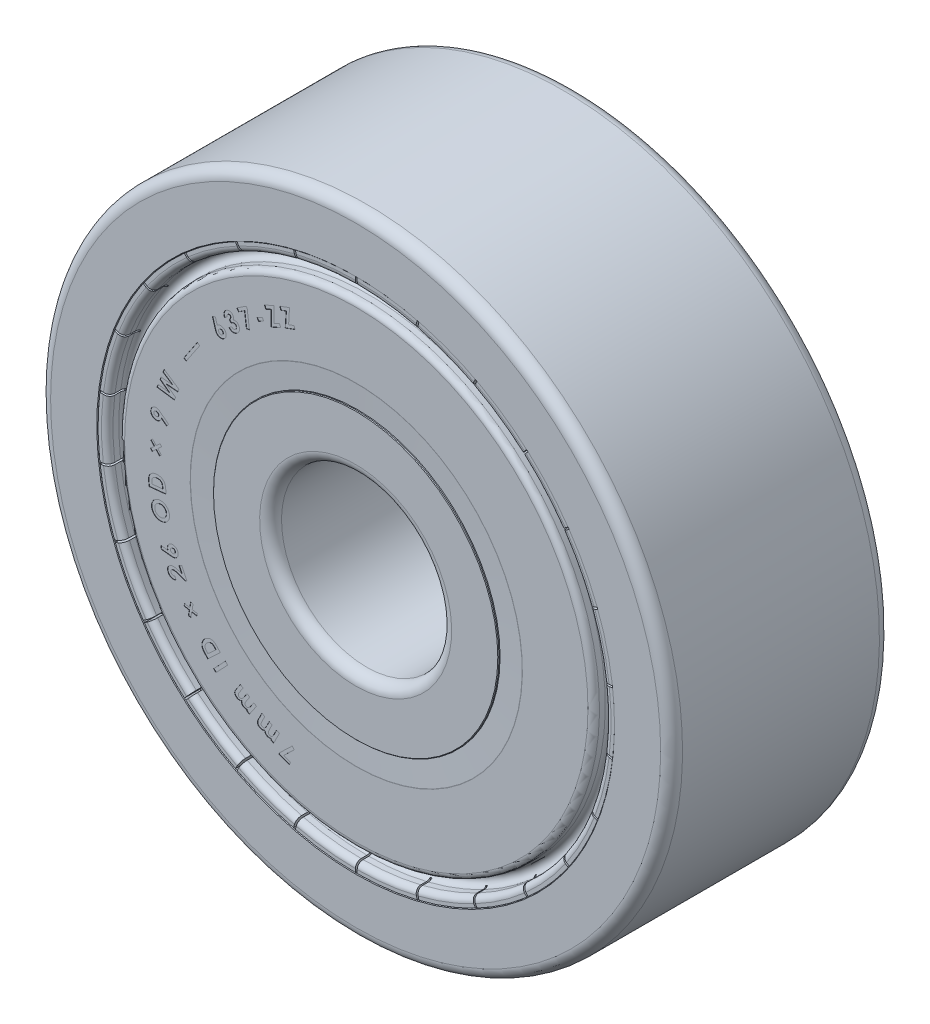
SolidWorks part; units mm, degrees
material "AISI 316 Annealed Stainless Steel Bar (SS)"
ref_plane "Front" through (0, 0, 0) normal (0, 0, 1) x (1, 0, 0)
ref_plane "Top" through (0, 0, 0) normal (0, 1, 0) x (1, 0, 0)
ref_plane "Right" through (0, 0, 0) normal (1, 0, 0) x (0, 0, -1)
sketch "LAYOUT R" plane through (0, 0, 0) normal (1, 0, 0) x (0, 0, -1)
  line L0 (-4.05, 3.5) -> (4.05, 3.5)
  line L1 (4.5, -13) -> (-4.5, -13) construction
  line L2 (4.5, -13) -> (4.5, 2.5781) construction
  line L3 (4.05, 13) -> (-4.05, 13)
  line L4 (-4.5, -13) -> (-4.5, 12.55) construction
  line L6 (2.6982, 0) -> (-2.6982, 0) construction
  line L7 (-4.474, 5.875) -> (4.474, 5.875)
  line L8 (-4.474, 10.625) -> (4.474, 10.625)
  line L11 (-8.89, 0) -> (8.89, 0) construction
  line L12 (-4.5, 12.55) -> (-4.5, 10.651)
  line L13 (4.5, 12.55) -> (4.5, 10.651)
  line L16 (-4.5, 5.849) -> (-4.5, 3.95)
  line L17 (4.5, 5.849) -> (4.5, 3.95)
  line L30 (-4.474, 10.625) -> (-4.474, 5.875) construction
  line L31 (4.474, 10.625) -> (4.474, 5.875) construction
  line L32 (-4.474, 6.825) -> (4.474, 6.825) construction
  line L33 (-4.4738, 6.825) -> (-4.4323, 5.875)
  line L34 (4.4738, 6.825) -> (4.4323, 5.875)
  line L35 (-4.474, 10.245) -> (4.474, 10.245) construction
  line L38 (-4.5, 10.651) -> (4.5, 10.651) construction
  line L39 (-4.474, 10.625) -> (-4.474, 10.4825)
  line L40 (-4.2365, 10.245) -> (-3.999, 10.245)
  line L41 (-4.474, 6.8354) -> (-4.474, 9.5325)
  line L42 (-4.2365, 9.77) -> (-3.999, 9.77)
  line L43 (4.474, 6.8354) -> (4.474, 9.5325)
  line L44 (4.2365, 9.77) -> (3.999, 9.77)
  line L45 (4.2365, 10.245) -> (3.999, 10.245)
  line L46 (-4.474, 9.77) -> (4.474, 9.77) construction
  line L50 (-1.3199, 9.675) -> (1.3199, 9.675) construction
  line L53 (4.474, 5.875) -> (4.5, 5.849)
  line L54 (-4.474, 5.875) -> (-4.5, 5.849)
  line L56 (-4.5, 5.849) -> (4.5, 5.849) construction
  line L57 (4.5, 10.651) -> (4.474, 10.625) construction
  line L58 (4.5, 10.651) -> (4.474, 10.625)
  line L60 (-4.5, 10.651) -> (-4.474, 10.625) construction
  line L61 (-4.5, 10.651) -> (-4.474, 10.625)
  line L64 (-3.999, 9.77) -> (-3.999, 10.245) construction
  line L65 (3.999, 9.77) -> (3.999, 10.245) construction
  line L66 (4.474, 10.625) -> (4.474, 10.4825)
  arc A2 (-4.2365, 9.77) -> (-4.474, 9.5325) centre (-4.2365, 9.5325) ccw
  arc A3 (4.474, 9.5325) -> (4.2365, 9.77) centre (4.2365, 9.5325) ccw
  arc A4 (4.4738, 6.825) -> (4.474, 6.8354) centre (4.2365, 6.8354) ccw
  arc A5 (-4.474, 6.8354) -> (-4.4738, 6.825) centre (-4.2365, 6.8354) ccw
  arc A6 (-3.999, 9.77) -> (-3.999, 10.245) centre (-3.999, 10.0075) ccw
  arc A7 (3.999, 10.245) -> (3.999, 9.77) centre (3.999, 10.0075) ccw
  arc A8 (-4.05, 13) -> (-4.5, 12.55) centre (-4.05, 12.55) ccw
  arc A9 (-4.5, 3.95) -> (-4.05, 3.5) centre (-4.05, 3.95) ccw
  arc A10 (4.05, 3.5) -> (4.5, 3.95) centre (4.05, 3.95) ccw
  arc A11 (-4.474, 10.4825) -> (-4.2365, 10.245) centre (-4.2365, 10.4825) ccw
  arc A12 (4.2365, 10.245) -> (4.474, 10.4825) centre (4.2365, 10.4825) ccw
  arc A13 (4.5, 12.55) -> (4.05, 13) centre (4.05, 12.55) ccw
  point P0 (0, 0)
  point P7 (-4.05, 13)
  point P8 (-4.2365, 10.245)
  point P15 (0, 0)
  point P29 (-4.474, 10.4825)
  point P38 (-4.4738, 6.825)
  point P54 (-4.474, 9.5325)
  point P55 (-4.2365, 9.77)
  point P56 (-4.474, 9.5325)
  point P58 (-4.474, 6.8354)
  point P59 (-4.4738, 6.825)
  point P60 (4.2365, 9.77)
  point P62 (4.474, 9.5325)
  point P63 (4.474, 6.8354)
  point P64 (4.4738, 6.825)
  point P71 (-4.5, 12.55)
  point P72 (-4.5, 3.95)
  point P73 (-4.05, 3.5)
  point P74 (4.05, 3.5)
  point P75 (4.5, 3.95)
  point P80 (4.05, 13)
  point P81 (4.2365, 10.245)
  point P88 (4.474, 10.4825)
  point P91 (4.5, 12.55)
  dimension "D21" = 0.475
  dimension "D33" = 0.45
  dimension "D3" = 3.5
  dimension "D4" = 5.875
  dimension "D5" = 10.625
  dimension "D24" = 9
  dimension "D6" = 8.974
  dimension "D7" = 8.974
  dimension "D11" = 0.95
  dimension "D12" = 2.5
  dimension "D13" = 2.5
  dimension "D14" = 0.38
  dimension "D17" = 0.026
  dimension "D18" = 0.475
  dimension "D19" = 0.475
  dimension "D20" = 0.475
  dimension "D15" = 0.95
  dimension "D23" = 45
  dimension "D25" = 45
  dimension "D27" = 0.026
  dimension "D28" = 13
  dimension "D29" = 9
  dimension "D30" = 26
  dimension "D8" = 4.5
  dimension "D31" = 45
  dimension "D32" = 45
sketch "Sketch R, INNER BODY" plane through (0, 0, 0) normal (1, 0, 0) x (0, 0, -1)
  line L1 (-4.474, 5.875) -> (-4.5, 5.849) construction
  line L3 (-4.5, 5.849) -> (-4.5, 3.95) construction
  line L12 (-8.89, 0) -> (8.89, 0) construction
  line L13 (-8.89, 0) -> (8.89, 0) construction
  line L14 (-4.05, 3.5) -> (4.05, 3.5) construction
  line L15 (4.5, 5.849) -> (4.5, 3.95) construction
  line L16 (4.474, 5.875) -> (4.5, 5.849) construction
  line L17 (-4.474, 5.875) -> (4.474, 5.875) construction
  line L18 (-4.474, 5.875) -> (-4.5, 5.849)
  line L19 (-4.5, 5.849) -> (-4.5, 3.95)
  line L20 (-4.05, 3.5) -> (4.05, 3.5)
  line L21 (4.5, 5.849) -> (4.5, 3.95)
  line L22 (4.474, 5.875) -> (4.5, 5.849)
  line L23 (-4.474, 5.875) -> (4.474, 5.875)
  arc A0 (-4.5, 3.95) -> (-4.05, 3.5) centre (-4.05, 3.95) ccw construction
  arc A1 (4.05, 3.5) -> (4.5, 3.95) centre (4.05, 3.95) ccw construction
  arc A2 (-4.5, 3.95) -> (-4.05, 3.5) centre (-4.05, 3.95) ccw
  arc A3 (4.05, 3.5) -> (4.5, 3.95) centre (4.05, 3.95) ccw
sketch "Sketch R, OUTER BODY" plane through (0, 0, 0) normal (1, 0, 0) x (0, 0, -1)
  line L8 (-8.89, 0) -> (8.89, 0) construction
  line L9 (-8.89, 0) -> (8.89, 0) construction
  line L31 (-4.5, 12.55) -> (-4.5, 10.651) construction
  line L84 (-4.5, 10.651) -> (-4.474, 10.625) construction
  line L85 (-4.474, 10.625) -> (4.474, 10.625) construction
  line L86 (4.5, 10.651) -> (4.474, 10.625) construction
  line L87 (4.5, 12.55) -> (4.5, 10.651) construction
  line L88 (4.05, 13) -> (-4.05, 13) construction
  line L89 (-4.5, 12.55) -> (-4.5, 10.651)
  line L90 (-4.5, 10.651) -> (-4.474, 10.625)
  line L91 (-4.474, 10.625) -> (4.474, 10.625)
  line L92 (4.5, 10.651) -> (4.474, 10.625)
  line L93 (4.5, 12.55) -> (4.5, 10.651)
  line L94 (4.05, 13) -> (-4.05, 13)
  arc A6 (4.5, 12.55) -> (4.05, 13) centre (4.05, 12.55) ccw construction
  arc A7 (-4.05, 13) -> (-4.5, 12.55) centre (-4.05, 12.55) ccw construction
  arc A8 (4.5, 12.55) -> (4.05, 13) centre (4.05, 12.55) ccw
  arc A9 (-4.05, 13) -> (-4.5, 12.55) centre (-4.05, 12.55) ccw
sketch "Sketch R, SHIELD FACES" plane through (0, 0, 0) normal (1, 0, 0) x (0, 0, -1)
  line L0 (-8.89, 0) -> (8.89, 0) construction
  line L1 (-8.89, 0) -> (8.89, 0) construction
  line L29 (-4.474, 10.625) -> (-4.474, 10.4825) construction
  line L32 (-4.2365, 10.245) -> (-3.999, 10.245) construction
  line L34 (-4.2365, 9.77) -> (-3.999, 9.77) construction
  line L36 (-4.474, 6.8354) -> (-4.474, 9.5325) construction
  line L38 (-4.4738, 6.825) -> (-4.4323, 5.875) construction
  line L39 (-4.474, 5.875) -> (4.474, 5.875) construction
  line L40 (4.4738, 6.825) -> (4.4323, 5.875) construction
  line L43 (4.474, 6.8354) -> (4.474, 9.5325) construction
  line L79 (4.2365, 9.77) -> (3.999, 9.77) construction
  line L80 (4.2365, 10.245) -> (3.999, 10.245) construction
  line L81 (4.474, 10.625) -> (4.474, 10.4825) construction
  line L82 (-4.474, 10.625) -> (4.474, 10.625) construction
  line L83 (-4.474, 10.625) -> (-4.474, 10.4825)
  line L84 (-4.2365, 10.245) -> (-3.999, 10.245)
  line L85 (-4.2365, 9.77) -> (-3.999, 9.77)
  line L86 (-4.474, 6.8354) -> (-4.474, 9.5325)
  line L87 (-4.4738, 6.825) -> (-4.4323, 5.875)
  line L88 (-4.4323, 5.875) -> (4.4323, 5.875)
  line L89 (4.4738, 6.825) -> (4.4323, 5.875)
  line L90 (4.474, 6.8354) -> (4.474, 9.5325)
  line L91 (4.2365, 9.77) -> (3.999, 9.77)
  line L92 (4.2365, 10.245) -> (3.999, 10.245)
  line L93 (4.474, 10.625) -> (4.474, 10.4825)
  line L94 (-4.474, 10.625) -> (4.474, 10.625)
  arc A28 (-4.474, 10.4825) -> (-4.2365, 10.245) centre (-4.2365, 10.4825) ccw construction
  arc A29 (-3.999, 9.77) -> (-3.999, 10.245) centre (-3.999, 10.0075) ccw construction
  arc A30 (-4.2365, 9.77) -> (-4.474, 9.5325) centre (-4.2365, 9.5325) ccw construction
  arc A31 (4.474, 9.5325) -> (4.2365, 9.77) centre (4.2365, 9.5325) ccw construction
  arc A32 (3.999, 10.245) -> (3.999, 9.77) centre (3.999, 10.0075) ccw construction
  arc A33 (4.2365, 10.245) -> (4.474, 10.4825) centre (4.2365, 10.4825) ccw construction
  arc A34 (-4.474, 10.4825) -> (-4.2365, 10.245) centre (-4.2365, 10.4825) ccw
  arc A35 (-3.999, 9.77) -> (-3.999, 10.245) centre (-3.999, 10.0075) ccw
  arc A36 (-4.2365, 9.77) -> (-4.474, 9.5325) centre (-4.2365, 9.5325) ccw
  arc A37 (4.474, 9.5325) -> (4.2365, 9.77) centre (4.2365, 9.5325) ccw
  arc A38 (3.999, 10.245) -> (3.999, 9.77) centre (3.999, 10.0075) ccw
  arc A39 (4.2365, 10.245) -> (4.474, 10.4825) centre (4.2365, 10.4825) ccw
  arc A40 (-4.474, 6.8354) -> (-4.4738, 6.825) centre (-4.2365, 6.8354) ccw construction
  arc A41 (-4.474, 6.8354) -> (-4.4738, 6.825) centre (-4.2365, 6.8354) ccw
  arc A42 (4.4738, 6.825) -> (4.474, 6.8354) centre (4.2365, 6.8354) ccw construction
  arc A43 (4.4738, 6.825) -> (4.474, 6.8354) centre (4.2365, 6.8354) ccw
revolve "Revolve INNER BODY" add sketch "Sketch R, INNER BODY" angle 360 about L13
revolve "Revolve OUTER BODY" add sketch "Sketch R, OUTER BODY" angle 360 about L9
revolve "Revolve SHIELDS" add sketch "Sketch R, SHIELD FACES" angle 360 about L1
sketch "Sketch TEXT RADIUS 1 — MANUALLY ASSIGN TEXT AND FONT SIZE (FROM EQUATIONS)" plane through (0, 0, 4.474) normal (0, 0, 1) x (1, 0, 0)
  circle A0 centre (0, 0) radius 7.895 construction
  text T0 "<b>7mm ID × 26 OD × 9 W  —  637-ZZ</b>" font "Century Gothic" height 0.71
  dimension "D1" = 15.79
extrude "Cut-Extrude LABEL 1" cut sketch "Sketch TEXT RADIUS 1 — MANUALLY ASSIGN TEXT AND FONT SIZE (FROM EQUATIONS)" against normal blind 0.0127
sketch "Sketch TEXT RADIUS 2 — MANUALLY ASSIGN TEXT AND FONT SIZE (FROM EQUATIONS)" plane through (0, 0, -4.474) normal (0, 0, -1) x (-1, 0, 0)
  circle A0 centre (0, 0) radius 7.895 construction
  text T0 "<b>7mm ID × 26 OD × 9 W  —  637-ZZ</b>" font "Century Gothic" height 0.71
  dimension "D1" = 15.79
extrude "Cut-Extrude LABEL 2" cut sketch "Sketch TEXT RADIUS 2 — MANUALLY ASSIGN TEXT AND FONT SIZE (FROM EQUATIONS)" against normal blind 0.0127
sketch "LAYOUT F, SLIT SEED" plane through (0, 0, 0) normal (0, 0, 1) x (1, 0, 0)
  line L0 (0, 0) -> (0, 12.7) construction
  line L3 (0.038, 10.6249) -> (0.038, 10.1925)
  line L4 (-0.038, 10.6249) -> (-0.038, 10.1925)
  circle A4 centre (0, 0) radius 10.15
  circle A5 centre (0, 0) radius 10.625
  circle A6 centre (0, 10.15) radius 0.057
  point P13 (-0.038, 10.6249)
  point P15 (0.038, 10.6249)
  dimension "D1" = 21.25
  dimension "D2" = 20.3
  dimension "D3" = 0.114
  dimension "D4" = 0.038
  dimension "D5" = 0.038
sketch "Sketch F, SLIT SEED" plane through (0, 0, 4.474) normal (0, 0, 1) x (1, 0, 0)
  line L1 (0.038, 10.6249) -> (0.038, 10.1925) construction
  line L8 (-0.038, 10.6249) -> (-0.038, 10.1925) construction
  line L9 (0.038, 10.6249) -> (0.038, 10.1925)
  line L10 (-0.038, 10.6249) -> (-0.038, 10.1925)
  circle A1 centre (0, 10.15) radius 0.057 construction
  circle A8 centre (0, 0) radius 10.625 construction
  arc A9 (-0.038, 10.1925) -> (0.038, 10.1925) centre (0, 10.15) ccw
  arc A10 (0.038, 10.6249) -> (-0.038, 10.6249) centre (0, 0) ccw
extrude "Cut-Extrude SLIT SEED F" cut sketch "Sketch F, SLIT SEED" along normal blind 0.635 from surface starting at face at (7.7653, 2.8704, -4.474)
extrude "Cut-Extrude SLIT SEED B" cut sketch "Sketch F, SLIT SEED<2>" against normal blind 0.635
sketch "Sketch F, SLIT SEED<2>" plane through (0, 0, 4.474) normal (0, 0, 1) x (1, 0, 0) same geometry as "Sketch F, SLIT SEED"
pattern_circular "CirPattern1" count 26 over 360 of "Cut-Extrude SLIT SEED F"
pattern_circular "CirPattern2" count 26 over 360 of "Cut-Extrude SLIT SEED B" reverse direction yes
equation "\"_i__BORE\" = 7"
equation "\"_i__OUTSIDE_DIAMETER\" = 26"
equation "\"_i__WIDTH\"= 9"
equation "\"_user_applied_FONT_SIZE\"= int ( \"BODY_SPAN__SHIELD__OF_RADIUS\" * \"g_param__FONT_SIZE_RATIO\" * 100 ) / 100'MANUALLY ASSIGN TO FONT"
equation "\"BODY__HALF_WIDTH\"= \"_i__WIDTH\" / 2"
equation "\"BODY_SPAN___OF_DIAMETER\"= \"_i__OUTSIDE_DIAMETER\" - \"_i__BORE\""
equation "\"BODY_SPAN___OF_RADIUS\"= \"BODY_SPAN___OF_DIAMETER\" / 2"
equation "\"BODY_SPAN__BORE_AND_OD__OF RADIUS\"= ( \"BODY_SPAN___OF_RADIUS\" - \"BODY_SPAN__SHIELD__OF_RADIUS\" ) / 2"
equation "\"BODY_SPAN__SHIELD__OF_RADIUS\"= \"BODY_SPAN___OF_RADIUS\" * \"g_param__SHIELD_PANEL_SPAN__RATIO_OF_BODY_RADIAN\""
equation "\"BORE__RADIUS\"= \"_i__BORE\" / 2"
equation "\"CORNER_RADII\"= \"_i__WIDTH\" * \"g_param__CORNER_RADII__RATIO_TO_WIDTH\""
equation "\"OUTSIDE_RADIUS\"= \"_i__OUTSIDE_DIAMETER\" / 2"
equation "\"RING_INNER__OUTSIDE_RADIUS\"= \"BORE__RADIUS\" + \"BODY_SPAN__BORE_AND_OD__OF RADIUS\""
equation "\"RING_OUTER__INSIDE_DIAMETER\"= \"RING_OUTER__INSIDE_RADIUS\" * 2"
equation "\"RING_OUTER__INSIDE_RADIUS\"= ( \"_i__OUTSIDE_DIAMETER\" / 2 ) - \"BODY_SPAN__BORE_AND_OD__OF RADIUS\""
equation "\"SHIELD__BOTTOM_AND_TOP_REGIONS_SPAN\"= \"BODY_SPAN__SHIELD__OF_RADIUS\" * \"g_param__SHIELD__TOP_AND_BOTTOM_REGIONS_RATIO\""
equation "\"SHIELD__COMPRESSION_FILLET_DIAMETER\"= \"BODY_SPAN__SHIELD__OF_RADIUS\" * \"g_param__SHIELD_COMPRESSION_FILLET_DIAMETER_RATIO\""
equation "\"SHIELD__COMPRESSION_FILLET_RADIUS\"= \"SHIELD__COMPRESSION_FILLET_DIAMETER\" / 2"
equation "\"SHIELD__FACE_FILLET_DIAMETER\"= \"BODY_SPAN__SHIELD__OF_RADIUS\" * \"g_param__SHIELD_FACE_FILLET_RATIO\""
equation "\"SHIELD__FACE_INSET\"= \"SIDE_FACE_CHAMFERS\""
equation "\"SHIELD__FACE_TO_OPPOSING_BRG_BODY_FACE\"= \"_i__WIDTH\" - \"SHIELD__FACE_INSET\""
equation "\"SHIELD__HALF_SLIT_WIDTH\"= \"SHIELD__SLIT_WIDTH\" / 2"
equation "\"SHIELD__HALF_WALL\"= \"SHIELD__WALL\" / 2"
equation "\"SHIELD__SLIT_WIDTH\"= \"SHIELD__WALL\" / 5"
equation "\"SHIELD__WALL\"= \"BODY_SPAN__SHIELD__OF_RADIUS\" * \"g_param__SHIELD_WALL_TO_SPAN_RATIO\""
equation "\"SHIELD_SLIT__INSIDE_TERMINUS__DIAMETER\"= \"RING_OUTER__INSIDE_DIAMETER\" - \"SHIELD__BOTTOM_AND_TOP_REGIONS_SPAN\""
equation "\"SHIELD_SLIT__KEYHOLE_DIAMETER\"= \"SHIELD__SLIT_WIDTH\" * 1.5"
equation "\"SIDE_FACE_CHAMFERS\"= \"_i__OUTSIDE_DIAMETER\" * \"g_param__SIDE_CHAMFERS__RATIO_TO_OD\""
equation "\"TEXT_RADIUS\"= \"_i__BORE\" + ( \"BODY_SPAN___OF_DIAMETER\" / 2 ) - \"_user_applied_FONT_SIZE\""
equation "\"WIDTH__HALF\"= \"_i__WIDTH\" / 2"
equation "\"D1@CirPattern1\" = \"g_param__SHIELD__NUMBER_OF_SLITS\""
equation "\"D1@CirPattern2\" = \"g_param__SHIELD__NUMBER_OF_SLITS\""
equation "\"D1@LAYOUT F, SLIT SEED\"=\"RING_OUTER__INSIDE_DIAMETER\""
equation "\"D1@Sketch TEXT RADIUS 1 — MANUALLY ASSIGN TEXT AND FONT SIZE (FROM EQUATIONS)\" = \"TEXT_RADIUS\""
equation "\"D1@Sketch TEXT RADIUS 2 — MANUALLY ASSIGN TEXT AND FONT SIZE (FROM EQUATIONS)\" = \"TEXT_RADIUS\""
equation "\"D11@LAYOUT R\"=\"SHIELD__BOTTOM_AND_TOP_REGIONS_SPAN\""
equation "\"D12@LAYOUT R\" = \"g_param__SHIELD__INSIDE_BEVEL_ANGLE__DEGREES\""
equation "\"D13@LAYOUT R\"= \"g_param__SHIELD__INSIDE_BEVEL_ANGLE__DEGREES\""
equation "\"D14@LAYOUT R\"=\"SHIELD__WALL\""
equation "\"D15@LAYOUT R\"=\"SHIELD__BOTTOM_AND_TOP_REGIONS_SPAN\""
equation "\"D17@LAYOUT R\"=\"SIDE_FACE_CHAMFERS\""
equation "\"D18@LAYOUT R\"=\"SHIELD__COMPRESSION_FILLET_DIAMETER\""
equation "\"D19@LAYOUT R\"=\"SHIELD__COMPRESSION_FILLET_DIAMETER\""
equation "\"D2@LAYOUT F, SLIT SEED\"=\"SHIELD_SLIT__INSIDE_TERMINUS__DIAMETER\""
equation "\"D20@LAYOUT R\"=\"SHIELD__COMPRESSION_FILLET_DIAMETER\""
equation "\"D21@LAYOUT R\"=\"SHIELD__FACE_FILLET_DIAMETER\""
equation "\"D24@LAYOUT R\"=\"_i__WIDTH\""
equation "\"D27@LAYOUT R\"=\"SIDE_FACE_CHAMFERS\""
equation "\"D28@LAYOUT R\"=\"OUTSIDE_RADIUS\""
equation "\"D3@LAYOUT F, SLIT SEED\"=\"SHIELD_SLIT__KEYHOLE_DIAMETER\""
equation "\"D3@LAYOUT R\"=\"BORE__RADIUS\""
equation "\"D30@LAYOUT R\"=\"_i__OUTSIDE_DIAMETER\""
equation "\"D33@LAYOUT R\"=\"CORNER_RADII\""
equation "\"D4@LAYOUT F, SLIT SEED\"=\"SHIELD__HALF_SLIT_WIDTH\""
equation "\"D4@LAYOUT R\"=\"RING_INNER__OUTSIDE_RADIUS\""
equation "\"D5@LAYOUT F, SLIT SEED\"=\"SHIELD__HALF_SLIT_WIDTH\""
equation "\"D5@LAYOUT R\"=\"RING_OUTER__INSIDE_RADIUS\""
equation "\"D6@LAYOUT R\"=\"SHIELD__FACE_TO_OPPOSING_BRG_BODY_FACE\""
equation "\"D7@LAYOUT R\"=\"SHIELD__FACE_TO_OPPOSING_BRG_BODY_FACE\""
equation "\"D8@LAYOUT R\"=\"WIDTH__HALF\""
equation "\"g_param__CORNER_RADII__RATIO_TO_WIDTH\"= 0.05'ISO MAX IS 0.07 WHERE WIDTH IS LESS THAN DIAMETER"
equation "\"g_param__FONT_SIZE_RATIO\"= 0.15'EXPRESSES RADIAL PROPORTION OF SHIELD FACE"
equation "\"g_param__INDICIA__EXTRUSION_DEPTH\"=0.013'CONCAVE-EMBOSSED INDICIA ON SHIELD FACES"
equation "\"g_param__SHIELD__INSIDE_BEVEL_ANGLE__DEGREES\"= 2.5'SHOULD BE GREATER THAN 0 AND LESS THAN OR EQUAL TO 10, ORIGINALLY 1"
equation "\"g_param__SHIELD__NUMBER_OF_SLITS\"=26'OPTIONAL NUMBER OF SHIELD COMPRESSION RING SLITS"
equation "\"g_param__SHIELD__TOP_AND_BOTTOM_REGIONS_RATIO\"=0.2'PART OF RADIAL SHIELD SPAN OCCUPIED BY INMOST BEVEL, ORIGINALLY 0.2"
equation "\"g_param__SHIELD_COMPRESSION_FILLET_DIAMETER_RATIO\"=0.1'ORIGINALLY 0,1"
equation "\"g_param__SHIELD_FACE_FILLET_RATIO\"=0.1'ORIGINALLY 0.1"
equation "\"g_param__SHIELD_FACE_INSET__RATIO_OF_WIDTH\"= 0.035'ISO-UNSPECIFIED, SHOULD BE AT LEAST 0.025 and LESS THAN 0.036"
equation "\"g_param__SHIELD_PANEL_SPAN__RATIO_OF_BODY_RADIAN\"= 0.5'ISO-UNSPECIFIED, ORIGINALLY 0.5"
equation "\"g_param__SHIELD_WALL_TO_SPAN_RATIO\"=0.08'SHOULD BE LESS THAN 0.015, ORIGINALLY 0.08, PRESCRIBES MATERIAL THICKNESS"
equation "\"g_param__SIDE_CHAMFERS__RATIO_TO_OD\"= 0.001'NOT ISO-SPECIFIED"
